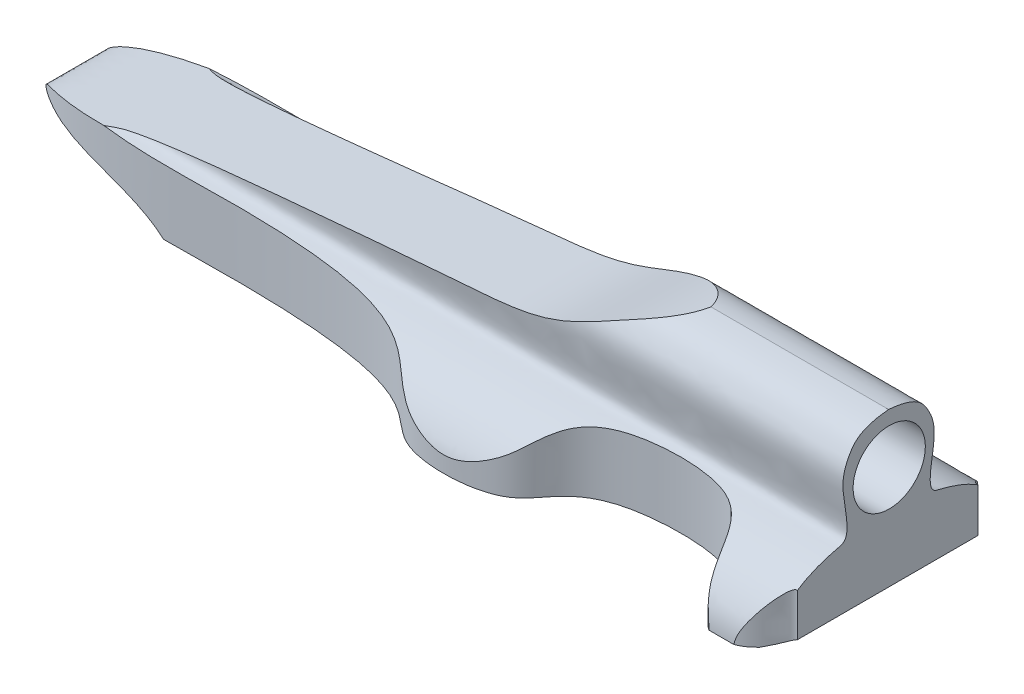
SolidWorks part; units mm, degrees
ref_plane "Front Plane" through (0, 0, 0) normal (0, 0, 1) x (1, 0, 0)
ref_plane "Top Plane" through (0, 0, 0) normal (0, 1, 0) x (1, 0, 0)
ref_plane "Right Plane" through (0, 0, 0) normal (1, 0, 0) x (0, 0, -1)
sketch "y face" plane through (0, 0, 0) normal (0, 1, 0) x (1, 0, 0)
  line L2 (17.1669, 8.247) -> (17.1669, -36.753)
  line L3 (17.1669, -14.253) -> (-189.8331, -14.253) construction
  spline S0 degree 3 poles (17.1669, 8.247) (15.7686, 7.9342) (12.2456, 15.9434) (-2.2985, 17.5446) (0.2439, -2.6959) (-45.9623, -2.0547) (-45.7717, 15.1001) (-87.8474, 15.8875) (-79.2087, -2.3094) (-161.9247, -0.4857) (-189.8007, -2.7002) (-189.8331, -14.253) knots 0 0 0 0 0.086967 0.163431 0.277715 0.35935 0.505285 0.650138 0.910692 0.923587 1 1 1 1
  spline S1 degree 3 poles (17.1669, -36.753) (15.7686, -36.4402) (12.2456, -44.4493) (-2.2985, -46.0505) (0.2439, -25.8101) (-45.9623, -26.4513) (-45.7717, -43.606) (-87.8474, -44.3935) (-79.2087, -26.1966) (-161.9247, -28.0202) (-189.8007, -25.8058) (-189.8331, -14.253) knots 0 0 0 0 0.086967 0.163431 0.277715 0.35935 0.505285 0.650138 0.910692 0.923587 1 1 1 1
  dimension "D1" = 207
  dimension "D2" = 45
  dimension "D3" = 45
extrude "Boss-Extrude1" add sketch "y face" along normal blind 111 and the other way blind 70 contours S1 L2 S0
sketch "z face" plane through (0, 0, 0) normal (0, 0, 1) x (1, 0, 0)
  line L1 (75.0817, 159.8421) -> (75.0817, 119.8421) construction
  line L2 (75.0817, 119.8421) -> (-94.9183, 119.8421) construction
  line L3 (-131.9183, 119.8421) -> (75.0817, 119.8421) construction
  line L4 (-131.9183, 119.8421) -> (-131.9183, 137.6337) construction
  line L5 (23.008, 157.8421) -> (19.4743, 148.8421) construction
  line L6 (75.008, 157.8421) -> (23.008, 157.8421) construction
  line L7 (75.008, 157.8421) -> (75.008, 139.8421) construction
  line L8 (75.008, 139.8421) -> (23.008, 139.8421) construction
  line L9 (23.008, 157.8421) -> (23.008, 139.8421) construction
  line L10 (19.4743, 148.8421) -> (23.008, 139.8421) construction
  line L11 (19.4743, 148.8421) -> (23.008, 148.8421) construction
  line L12 (-94.9183, 119.8421) -> (49.6861, 119.8421)
  line L13 (75.0817, 159.8421) -> (75.0817, 129.3138)
  spline S0 degree 3 poles (75.0817, 159.8421) (67.8994, 167.1637) (18.6252, 164.1403) (0.9165, 147.8412) (-27.6289, 146.3434) (-58.1582, 143.1459) (-91.6849, 139.9265) (-131.926, 135.6297) (-131.9202, 133.5457) (-120.6512, 128.2686) (-103.4119, 129.1096) (-94.9183, 119.8421) knots 0 0 0 0 0.194716 0.404264 0.513482 0.56439 0.666184 0.685802 0.704646 0.715271 1 1 1 1
  spline S1 degree 2 poles (75.0817, 129.3138) (75.046, 119.9641) (49.6861, 119.8421) knots 0 0 0 1 1 1
  point P16 (23.008, 148.8421)
  dimension "D1" = 170
  dimension "D2" = 40
  dimension "D3" = 52
  dimension "D4" = 52
  dimension "D5" = 207
  dimension "D6" = 207
  dimension "D7" = 18
  dimension "D8" = 20
extrude "Boss-Extrude2" add sketch "z face" along normal blind 193 and the other way blind 145 contours S0 L12 S1 L13
sketch "x face" plane through (0, 0, 0) normal (1, 0, 0) x (0, 0, -1)
  line L1 (-43.8459, -903.9667) -> (-43.8459, 49096.0333) construction
  line L2 (-14.019, 213.3763) -> (-14.019, 173.3763) construction
  line L3 (15.981, 173.3763) -> (-44.019, 173.3763)
  line L4 (-14.019, 202.3763) -> (-7.3389, 196.345) construction
  line L5 (-14.019, 202.3763) -> (-14.019, 173.3763) construction
  line L6 (-36.1472, 223.3763) -> (11.1934, 223.3763) construction
  line L7 (15.981, 237.8756) -> (15.981, 50237.8756) construction
  circle A0 centre (-14.019, 202.3763) radius 9 construction
  spline S0 degree 3 poles (-14.019, 213.3763) (-7.3436, 212.8131) (-2.9421, 207.4813) (-2.0617, 201.0423) (-4.8601, 190.4214) (0.785, 189.4284) (15.3033, 184.9967) (15.981, 173.3763) knots 0 0 0 0 0.156455 0.396872 0.669473 0.736508 1 1 1 1
  spline S1 degree 3 poles (-14.019, 213.3763) (-20.6943, 212.8131) (-25.0958, 207.4813) (-25.9762, 201.0423) (-23.1778, 190.4214) (-28.823, 189.4284) (-43.3412, 184.9967) (-44.019, 173.3763) knots 0 0 0 0 0.156455 0.396872 0.669473 0.736508 1 1 1 1
  dimension "D1" = 30
  dimension "D2" = 40
  dimension "D3" = 9
  dimension "D4" = 29
  dimension "D5" = 50
extrude "Boss-Extrude4" add sketch "x face" along normal blind 89 and the other way blind 274
move or copy body "Body-Move/Copy3" bodies to move or copy 103 copy no translate (-53.3352, -73.7117, 0)
move or copy body "Body-Move/Copy5" bodies to move or copy 110 copy no translate (0, -59.6026, 0)
move or copy body "Body-Move/Copy6" bodies to move or copy 109 copy no translate (-67.2723, -185.32, 0)
combine bodies "Combine3" operation type common bodies to combine 113 101 115
sketch "Sketch4" plane through (0, 0, 0) normal (0, 1, 0) x (1, 0, 0)
  line L0 (19.7526, 21.1912) -> (19.7526, -49978.8088) construction
  line L1 (-65.0574, -13.8451) -> (49934.9426, -13.8451) construction
sketch "Sketch5" plane through (0, 0, 0) normal (1, 0, 0) x (0, 0, -1)
  line L1 (-13.8713, 15.5066) -> (-13.8713, -13.4934) construction
  line L3 (-13.8713, 15.5066) -> (-5.4677, 18.7285) construction
  circle A0 centre (-13.8713, 15.5066) radius 9
  dimension "D1" = 9
  dimension "D2" = 29
extrude "Cut-Extrude2" cut sketch "Sketch5" against normal blind 52 from offset 22
fillet "Fillet6" [suppressed] radius 10 tangent propagation no
sketch "Sketch6" plane through (-10.8498, -13.4934, 13.8713) normal (0, 1, 0) x (0, 0, -1)
  line L1 (-2.9738, -27.3556) -> (3.0262, -27.3556)
  line L2 (-2.9738, -27.3556) -> (-2.9738, 178.6433)
  line L3 (-2.9738, 178.6433) -> (3.0262, 178.6433)
  line L4 (3.0262, -27.3556) -> (3.0262, 178.6433)
  line L5 (0.0262, 200054.2076) -> (0.0262, -249945.7924) construction
  point P7 (0.0262, 178.6433)
  dimension "D1" = 6
extrude "Cut-Extrude3" cut sketch "Sketch6" along normal blind 6
combine bodies "Combine2" [suppressed] operation type common bodies to combine 111 110 111
